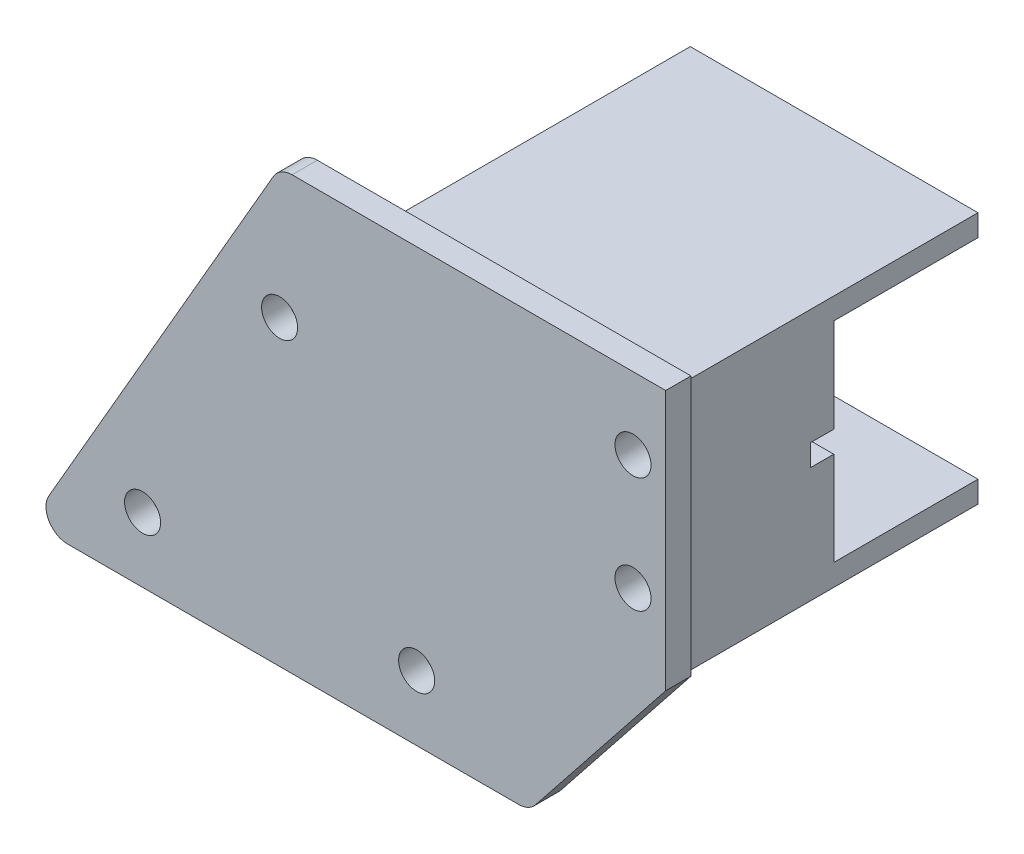
SolidWorks part; units mm, degrees
ref_plane "Front Plane" through (0, 0, 0) normal (0, 0, 1) x (1, 0, 0)
ref_plane "Top Plane" through (0, 0, 0) normal (0, 1, 0) x (1, 0, 0)
ref_plane "Right Plane" through (0, 0, 0) normal (1, 0, 0) x (0, 0, -1)
sketch "Sketch1" plane through (0, 0, 0) normal (0, 0, 1) x (1, 0, 0)
  line L0 (-32.7569, -9) -> (36.42, -9)
  line L1 (36.42, -9) -> (55.3674, 14.8487)
  line L2 (1.8315, 50.909) -> (-32.7569, -9)
  line L3 (55.3674, 14.8487) -> (55.3674, 50.909)
  line L4 (55.3674, 50.909) -> (1.8315, 50.909)
  circle A0 centre (-17.1685, 0) radius 2.5
  circle A1 centre (20.8315, 0) radius 2.5
  circle A2 centre (1.8315, 32.909) radius 2.5
  point P6 (50.9989, 14.1919)
  point P12 (54.6441, 16.9258)
  point P13 (0, 0)
  point P14 (56.1366, 17.5709)
  point P15 (0, 0)
  point P16 (55.3954, 16.568)
  point P17 (55.3674, 14.8487)
  dimension "D5" = 5
  dimension "D1" = 38
  dimension "D2" = 38
  dimension "D3" = 38
  dimension "D4" = 9
  dimension "D6" = 9
extrude "Boss-Extrude1" add sketch "Sketch1" along normal blind 3.5
fillet "Fillet1" radius 3 3 edges at (-32.7569, -9, 1.75) (1.8315, 50.909, 1.75) (36.42, -9, 1.75)
sketch "Sketch2" plane through (0, 0, 0) normal (0, 0, -1) x (-1, 0, 0)
  line L0 (-55.1719, 32.909) -> (20.3281, 32.909) construction
  line L1 (-55.1719, 47.409) -> (20.3281, 47.409)
  line L2 (-55.1719, 47.409) -> (-55.1719, 18.409)
  line L3 (-55.1719, 18.409) -> (20.3281, 18.409)
  line L4 (20.3281, 47.409) -> (20.3281, 18.409)
  line L5 (-55.1719, 47.409) -> (20.3281, 18.409) construction
  line L6 (-55.1719, 18.409) -> (20.3281, 47.409) construction
  line L7 (-46.8315, 47.409) -> (-46.8315, 18.409)
  line L8 (12.1685, 47.409) -> (12.1685, 18.409)
  line L9 (16.1685, 47.409) -> (16.1685, 18.409) construction
  line L10 (-50.8315, 47.409) -> (-50.8315, 18.409) construction
  line L11 (12.1685, 34.409) -> (20.3281, 34.409)
  line L12 (20.3281, 34.409) -> (20.3281, 31.409)
  line L13 (20.3281, 31.409) -> (12.1685, 31.409)
  line L14 (-46.8315, 34.409) -> (-55.1719, 34.409)
  line L15 (-46.8315, 31.409) -> (-55.1719, 31.409)
  line L16 (-46.8315, 47.409) -> (12.1685, 18.409) construction
  line L17 (12.1685, 18.409) -> (12.1685, 47.409) construction
  line L18 (12.1685, 47.409) -> (-46.8315, 18.409) construction
  line L19 (-15.2762, 47.409) -> (-15.2762, 18.409)
  line L20 (-55.1719, 47.409) -> (-15.2762, 47.409)
  line L21 (-55.1719, 47.409) -> (-55.1719, 50.409)
  line L22 (-55.1719, 50.409) -> (-15.2762, 50.409)
  line L23 (-15.2762, 47.409) -> (-15.2762, 50.409)
  line L24 (-55.1719, 18.409) -> (16.1685, 18.409)
  line L25 (-55.1719, 18.409) -> (-11.2524, 18.409)
  line L26 (-55.1719, 18.409) -> (-55.1719, 15.409)
  line L27 (-55.1719, 15.409) -> (-11.2524, 15.409)
  line L28 (-11.2524, 18.409) -> (-11.2524, 15.409)
  circle A0 centre (-1.8315, 32.909) radius 4.125
  circle A1 centre (16.1685, 40.909) radius 2.5
  circle A2 centre (16.1685, 24.909) radius 2.5
  circle A3 centre (-50.8315, 24.909) radius 2.5
  circle A4 centre (-50.8315, 40.909) radius 2.5
  point P0 (-17.4219, 32.909)
  point P26 (-17.3315, 32.909)
  dimension "D2" = 8.25
  dimension "D12" = 5
  dimension "D1" = 75.5
  dimension "D3" = 14
  dimension "D4" = 45
  dimension "D5" = 67
  dimension "D6" = 3
  dimension "D7" = 1.5
  dimension "D8" = 3
  dimension "D9" = 4
  dimension "D10" = 4
  dimension "D11" = 59
  dimension "D13" = 16
  dimension "D14" = 16
  dimension "D15" = 8
  dimension "D16" = 8
  dimension "D17" = 29
  dimension "D18" = 3
  dimension "D19" = 3
extrude "Boss-Extrude2" add sketch "Sketch2" against normal blind 3.5 contours A4 | A3 | A2 | A1 | L1 L4 L3 L2 | A0 region at (-16.1685, 40.909, 0) region at (-16.1685, 24.909, 0) region at (50.8315, 24.909, 0) region at (50.8315, 40.909, 0)
extrude "Boss-Extrude3" add sketch "Sketch2<4>" along normal blind 20 contours L14 L7 L1 L2 A4 | L7 L15 L2 L3 A3 | L28 L3 L26 L27 | L21 L22 L23 L20 region at (51.0017, 47.2545, 0) region at (51.0017, 31.2545, 0) region at (33.2121, 16.909, 0)
sketch "Sketch2<4>" plane through (0, 0, 0) normal (0, 0, -1) x (-1, 0, 0) same geometry as "Sketch2"
fillet "Fillet2" radius 3 1 edges at (-16.9324, 18.409, 1.75)
fillet "Fillet3" [suppressed] radius 3
extrude "Boss-Extrude5" add sketch "Sketch2<7>" along direction (0, 0, -1) on the side of the normal offset from surface (16.8 mm away) 3.2 contours L15 L7 L14 L2 region at (51.0017, 32.909, 0) up to face at (48.3315, 24.909, -20)
sketch "Sketch2<7>" plane through (0, 0, 0) normal (0, 0, -1) x (-1, 0, 0) same geometry as "Sketch2"
sketch "Sketch3" plane through (0, 0, 0) normal (0, 0, -1) x (-1, 0, 0)
  line L0 (-1.8315, 50.909) -> (32.7569, -9) construction
  line L1 (-1.8315, 50.909) -> (32.7569, -9)
  line L2 (32.7569, -9) -> (32.7569, 50.909)
  line L3 (32.7569, 50.909) -> (-1.8315, 50.909)
extrude "Cut-Extrude3" cut sketch "Sketch2<9>" against normal through all contours A4 | A3 region at (50.8315, 24.909, 0) region at (50.8315, 40.909, 0)
sketch "Sketch2<9>" plane through (0, 0, 0) normal (0, 0, -1) x (-1, 0, 0) same geometry as "Sketch2"
extrude "Cut-Extrude1" cut sketch "Sketch3" against normal through all
extrude "Boss-Extrude6" add sketch "Sketch2<10>" along normal blind 40 contours L1 L23 L22 L21 | L28 L3 L26 L27 region at (35.224, 48.909, 0) region at (33.2121, 16.909, 0)
sketch "Sketch2<10>" plane through (0, 0, 0) normal (0, 0, -1) x (-1, 0, 0) same geometry as "Sketch2"
equation "\"D2@Sketch1\"=\"D1@Sketch1\""
equation "\"D3@Sketch1\"=\"D1@Sketch1\""
equation "\"D6@Sketch1\"=\"D4@Sketch1\""
equation "\"D7@Sketch2\"=\"D6@Sketch2\"/2"
equation "\"D8@Sketch2\"=3"
